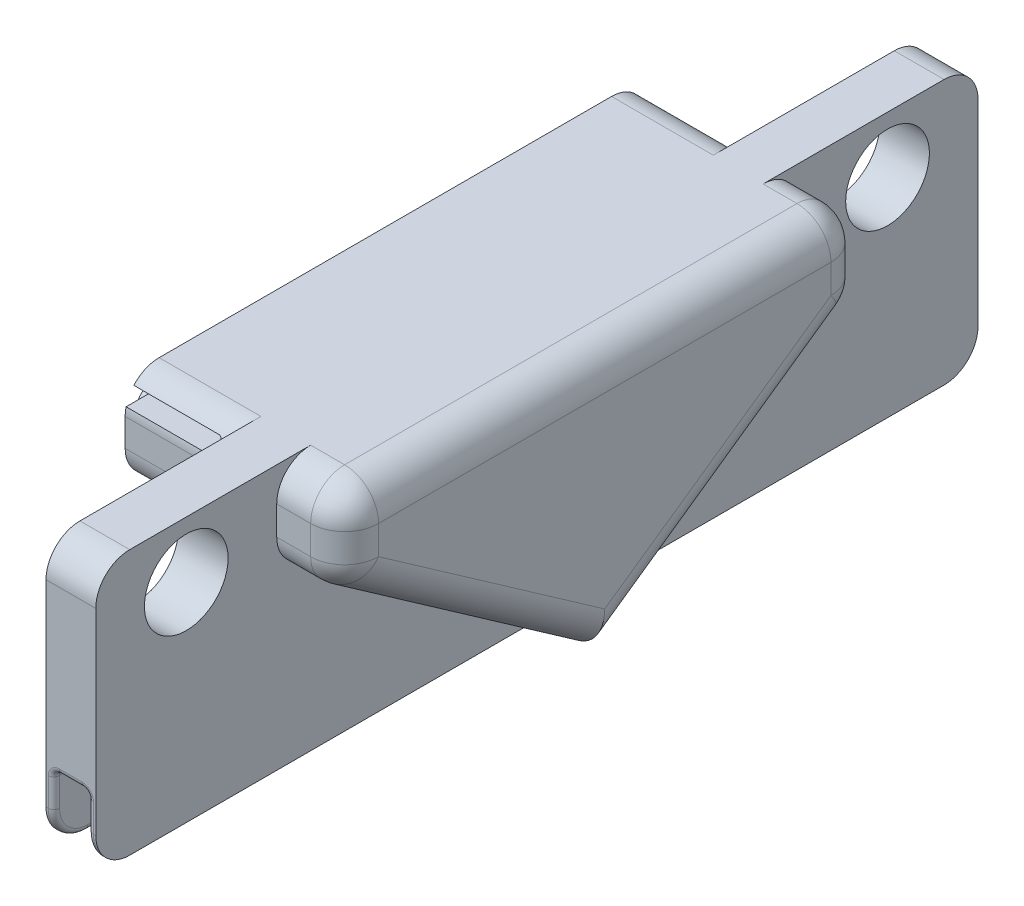
SolidWorks part; units mm, degrees
note: The reader was unsure of these and kept them because the rebuilt part matched: shared geometry of "Sketch7<4>", "Sketch7<5>", "Sketch7<6>".
ref_plane "Front Plane" through (0, 0, 0) normal (0, 0, 1) x (1, 0, 0)
ref_plane "Top Plane" through (0, 0, 0) normal (0, 1, 0) x (1, 0, 0)
ref_plane "Right Plane" through (0, 0, 0) normal (1, 0, 0) x (0, 0, -1)
sketch "Sketch1" plane through (0, 0, 0) normal (0, 1, 0) x (1, 0, 0)
  line L0 (-28.7782, 14.0442) -> (-24.2782, 14.0442)
  line L1 (-24.2782, 14.0442) -> (-24.2782, 22.0442)
  line L2 (-24.2782, 22.0442) -> (-22.0782, 22.0442)
  line L3 (-22.0782, 22.0442) -> (-22.0782, 14.0442)
  line L4 (-22.0782, 14.0442) -> (-19.0782, 14.0442)
  line L5 (-19.0782, 14.0442) -> (-19.0782, 2.5442)
  line L7 (-19.0782, 2.5442) -> (-28.7782, 2.5442)
  line L9 (-28.7782, 2.5442) -> (-28.7782, 14.0442)
  dimension "D1" = 9.7
  dimension "D2" = 3
  dimension "D3" = 8
  dimension "D4" = 11.5
extrude "Boss-Extrude1" add sketch "Sketch1" along normal blind 11.7
sketch "Sketch7" plane through (-28.7782, 0, 0) normal (-1, 0, 0) x (0, 0, 1)
  line L0 (-14.0442, 11.7) -> (-14.0442, -1.2986) construction
  line L5 (-14.0442, 11.7) -> (-14.0442, 8.2)
  line L6 (-10.7942, 10.0986) -> (-10.7942, 6.3014) construction
  line L7 (-10.7942, 8.2) -> (-15.8582, 8.2) construction
  line L8 (-14.0442, 8.2) -> (-2.5442, 0.0973)
  line L9 (-2.5442, 0.0973) -> (-2.5442, 11.7)
  line L10 (-2.5442, 11.7) -> (-14.0442, 11.7)
  line L11 (-2.5442, 11.2) -> (-14.0442, 11.2)
  line L12 (-14.0442, 11.2) -> (-14.0442, 10.55)
  line L13 (-14.0442, 8.2) -> (-14.0442, 0)
  line L14 (-14.0442, 10.55) -> (-2.5442, 10.55)
  line L15 (-2.5442, 10.55) -> (-2.5442, 11.2)
  line L16 (-14.0442, 0) -> (-2.5442, 0)
  line L17 (-2.5442, 0) -> (-2.5442, 0.0973)
  line L18 (-2.5442, 0.0973) -> (-14.0442, 8.2)
  line L19 (-14.0442, 0) -> (-14.0442, 8.2)
  line L20 (-14.0442, 8.2) -> (-22.0442, 10.2) construction
  line L22 (-2.5442, 11.7) -> (-14.0442, 11.7) construction
  line L23 (-18.0442, 11.7) -> (-18.0442, 0) construction
  line L24 (-22.0442, 11.7) -> (-14.0442, 11.7) construction
  line L25 (-22.0442, 0) -> (-14.0442, 0) construction
  line L26 (-22.0442, 11.7) -> (-22.0442, 0) construction
  circle A0 centre (-10.7942, 8.2) radius 1.6
  circle A1 centre (-18.0442, 9.2) radius 1.85
  line M20 (-14.0442, 0) -> (-2.5442, 0)
  line M21 (-2.5442, 0) -> (-2.5442, 11.7)
  line M23 (-14.0442, 11.7) -> (-14.0442, 0)
  dimension "D2" = 0.5
  dimension "D4" = 3.5
  dimension "D5" = 3.25
  dimension "D6" = 0.65
  dimension "D7" = 3.5
  dimension "D8" = 4
extrude "Cut-Extrude2" cut sketch "Sketch7" against normal blind 4 contours L15 L11 L12 L14
extrude "Boss-Extrude2" add sketch "Sketch7<4>" along normal blind 1.4 contours A0
sketch "Sketch7<4>" plane through (-28.7782, 0, 0) normal (-1, 0, 0) x (0, 0, 1) same geometry as "Sketch7"
extrude "Cut-Extrude3" cut sketch "Sketch7<5>" against normal up to surface (4.5 mm away) contours L8 M23 M20 M21 up to face at (-24.2782, 5.85, -18.0442)
sketch "Sketch7<5>" plane through (-28.7782, 0, 0) normal (-1, 0, 0) x (0, 0, 1) same geometry as "Sketch7"
extrude "Cut-Extrude4" cut sketch "Sketch7<6>" against normal through all and the other way through all contours A1
sketch "Sketch7<6>" plane through (-28.7782, 0, 0) normal (-1, 0, 0) x (0, 0, 1) same geometry as "Sketch7"
sketch "Sketch10" plane through (-22.0782, 0, 0) normal (1, 0, 0) x (0, 0, -1)
  line L1 (15.5442, 9.2) -> (15.5442, 0)
  line L3 (15.5442, 0) -> (2.5442, 0)
  line L4 (2.5442, 0) -> (2.5442, 0.0973)
  line L7 (2.5442, 0.0973) -> (15.5442, 9.2)
  dimension "D1" = 13
  dimension "D2" = 9.2
extrude "Cut-Extrude5" cut sketch "Sketch10" along normal up to surface (3 mm away) from surface
sketch "Sketch12" plane through (0, 0, 0) normal (0, -1, 0) x (1, 0, 0)
  line L0 (-23.1782, -22.0442) -> (-23.1782, -1.0435) construction
  line L3 (-22.0782, -22.0442) -> (-24.2782, -22.0442) construction
  line L8 (-22.0782, -12.2942) -> (-24.2782, -12.2942) construction
  line L9 (-22.0782, -2.5442) -> (-22.0782, -22.0442) construction
  line L10 (-24.2782, -22.0442) -> (-24.2782, -2.5442) construction
  line L12 (-23.9282, -1.0435) -> (-22.4282, -1.0435)
  line L13 (-23.9282, -1.0435) -> (-23.9282, -22.0442)
  line L14 (-23.9282, -22.0442) -> (-22.4282, -22.0442)
  line L15 (-22.4282, -1.0435) -> (-22.4282, -22.0442)
  line L16 (-23.9282, -1.0435) -> (-22.4282, -22.0442) construction
  line L17 (-23.9282, -22.0442) -> (-22.4282, -1.0435) construction
  point P6 (-23.1782, -1.0435)
  point P11 (-23.1782, -11.5439)
  dimension "D1" = 0.75
extrude "Cut-Extrude6" cut sketch "Sketch12" against normal blind 3
sketch "Sketch14" plane through (0, 0, 0) normal (0, -1, 0) x (-1, 0, 0)
  line L1 (24.2782, 2.5442) -> (22.0782, 2.5442)
  line L2 (24.2782, 2.5442) -> (24.2782, 6.5442)
  line L3 (24.2782, 6.5442) -> (22.0782, 6.5442)
  line L4 (22.0782, 2.5442) -> (22.0782, 6.5442)
  line L5 (24.2782, 22.0442) -> (24.2782, 2.5442) construction
  line L6 (22.0782, 14.0442) -> (22.0782, 2.5442) construction
  dimension "D1" = 4
extrude "Boss-Extrude3" add sketch "Sketch14" against normal blind 1
fillet "Fillet3" radius 1.5 10 edges at (-26.5282, 8.2, -14.0442) (-20.5782, 8.1497, -14.0442) (-26.5282, 11.7, -14.0442) (-20.5782, 11.7, -14.0442) (-19.0782, 4.1235, -8.2942) (-19.0782, 9.9248, -14.0442) (-19.0782, 11.7, -8.2942) (-23.1782, 11.7, -22.0442) (-24.1032, 0, -22.0442) (-22.2532, 0, -22.0442)
mirror "Mirror3" about plane through (-19.0782, 11.7, -2.5442) normal (0, 0, -1) of bodies 110
fillet "Fillet4" radius 0.25 28 edges at (-22.4282, 3, -2.5442) (-23.9282, 3, -2.5442) (-23.9282, 2.25, -22.0442) (-23.1782, 3, -22.0442) (-22.4282, 2.25, -22.0442) (-23.9282, 0, -13.5442) (-23.9282, 1, -2.5442) (-23.9282, 0.5, -6.5442) (-23.1782, 1, -6.5442) (-22.4282, 0.5, -6.5442) (-22.4282, 1, -2.5442) (-23.1782, 0, -6.5442) (-22.4282, 0, -13.5442) (-23.9282, 0.4393, -21.6049) (-22.4282, 0.4393, -21.6049) (-24.7782, 10.55, -2.5442) (-23.1782, 3, 16.9558) (-22.4282, 2.25, 16.9558) (-22.4282, 0, 8.4558) (-23.9282, 0, 8.4558) (-23.9282, 2.25, 16.9558) (-22.4282, 0.5, 1.4558) (-23.9282, 0.5, 1.4558) (-23.1782, 0, 1.4558) (-23.1782, 1, 1.4558) (-23.9282, 0.4393, 16.5165) (-22.4282, 0.4393, 16.5165) (-24.7782, 11.2, -2.5442)
